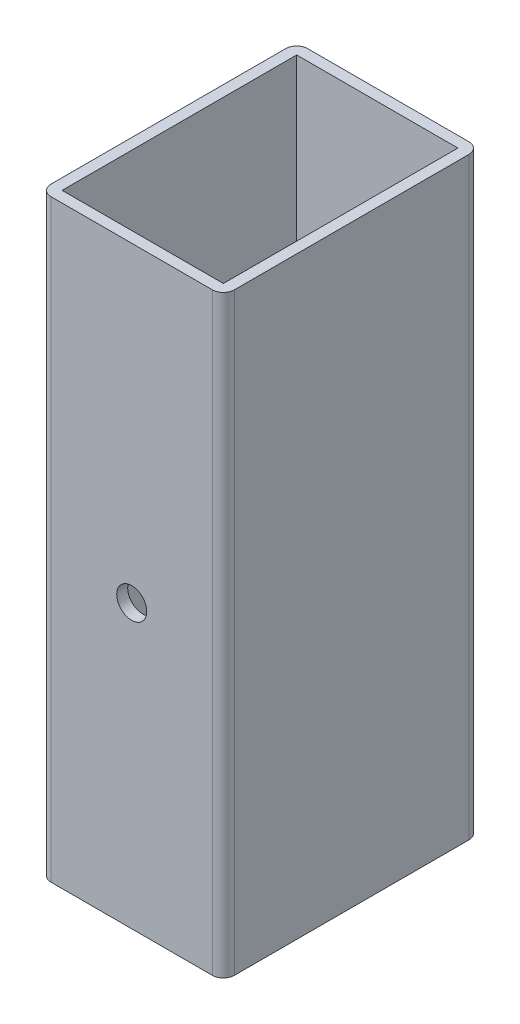
SolidWorks part; units mm, degrees
ref_plane "前视基准面" through (0, 0, 0) normal (0, 0, 1) x (1, 0, 0)
ref_plane "上视基准面" through (0, 0, 0) normal (0, 1, 0) x (1, 0, 0)
ref_plane "右视基准面" through (0, 0, 0) normal (1, 0, 0) x (0, 0, -1)
other "Configuration Table"
sketch "草图1" plane through (0, 0, 0) normal (0, 0, 1) x (1, 0, 0)
  line L0 (0, 0) -> (50, 0)
  line L1 (50, 0) -> (50, 162)
  line L2 (50, 162) -> (0, 162)
  line L3 (0, 162) -> (0, 0)
  dimension "width" = 50
  dimension "height" = 162
extrude "BlockExtrude" add sketch "草图1" along normal blind 70
fillet "Fillet" radius 3 4 edges at (0, 81, 0) (50, 81, 0) (0, 81, 70) (50, 81, 70) tangent propagation no
shell "抽壳1" thickness 3 removed face at (25, 162, 35)
sketch "草图2" plane through (0, 0, 0) normal (0, 0, -1) x (-1, 0, 0)
  circle A0 centre (-25, 77) radius 4.1
  dimension "diameter" = 8.2
  dimension "x" = 25
  dimension "y" = 77
extrude "Cable_entry" cut sketch "草图2" against normal through all
